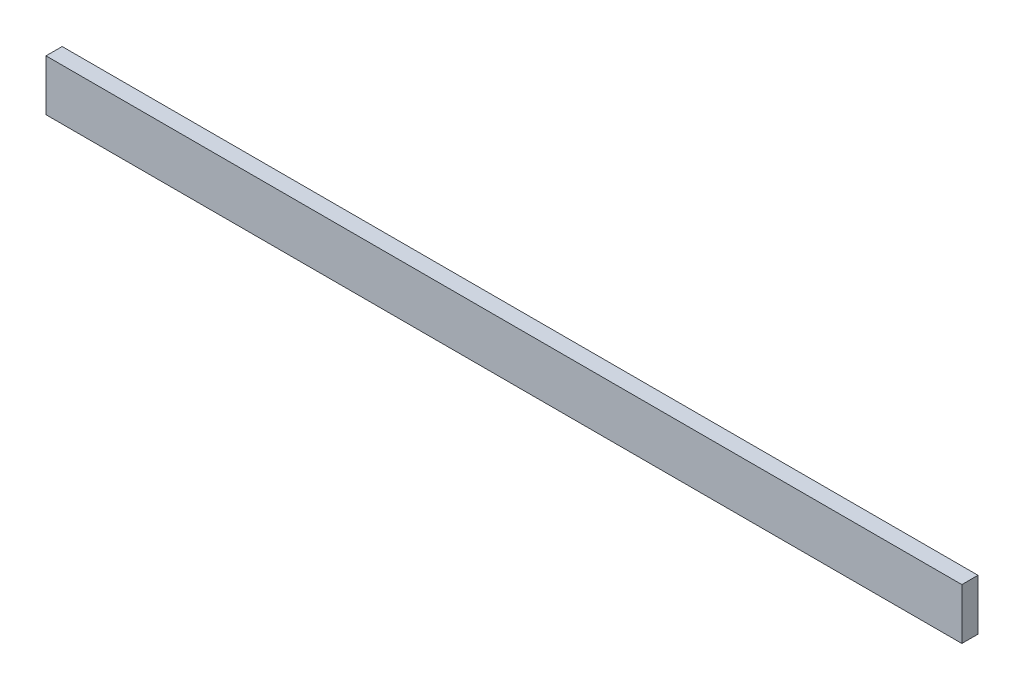
SolidWorks part; units mm, degrees
ref_plane "Front" through (0, 0, 0) normal (0, 0, 1) x (1, 0, 0)
ref_plane "Top" through (0, 0, 0) normal (0, 1, 0) x (1, 0, 0)
ref_plane "Right" through (0, 0, 0) normal (1, 0, 0) x (0, 0, -1)
sketch "Sketch1" plane through (0, 0, 0) normal (0, 1, 0) x (1, 0, 0)
  line L5 (1077.2, 9.5) -> (1077.2, -9.5) construction
  line L6 (1077.2, 9.5) -> (0, 9.5)
  line L7 (1077.2, 9.5) -> (1077.2, -9.5)
  line L8 (1077.2, -9.5) -> (0, -9.5)
  line L9 (0, 9.5) -> (0, -9.5)
  line L10 (1077.2, 9.5) -> (0, -9.5) construction
  line L11 (1077.2, -9.5) -> (0, 9.5) construction
  point P0 (538.6, 0)
  dimension "D1" = 19
extrude "Boss-Extrude1" add sketch "Sketch1" along normal blind 60
